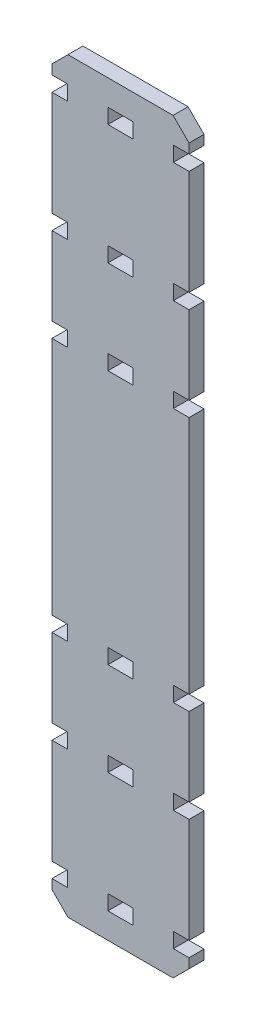
SolidWorks part; units mm, degrees
ref_plane "Front" through (0, 0, 0) normal (0, 0, 1) x (1, 0, 0)
ref_plane "Top" through (0, 0, 0) normal (0, 1, 0) x (1, 0, 0)
ref_plane "Right" through (0, 0, 0) normal (1, 0, 0) x (0, 0, -1)
ref_axis "side-side" through (80.9, 0, 0) along (-1, 0, 0)
ref_axis "up-down" through (0, 50, 0) along (0, -1, 0)
ref_axis "front-back" through (0, 0, -80.9) along (0, 0, 1)
sketch "Sketch1" plane through (0, 0, 0) normal (0, 0, 1) x (1, 0, 0)
  line L0 (21.7993, 110.6625) -> (21.7993, 118.7905) construction
  line L1 (43.5986, 118.7905) -> (0, 118.7905)
  line L2 (43.5986, 118.7905) -> (43.5986, 110.6625)
  line L3 (43.5986, -118.7905) -> (0, -118.7905)
  line L4 (0, 118.7905) -> (0, 110.6625)
  line L5 (25.7993, 110.6625) -> (17.7993, 110.6625)
  line L6 (5, 110.6625) -> (-15, 110.6625) construction
  line L7 (0, -110.6625) -> (5, -110.6625) construction
  line L8 (43.5986, 105.9) -> (38.5986, 105.9) construction
  line L9 (0, 110.6625) -> (5, 110.6625)
  line L10 (25.7993, 110.6625) -> (25.7993, 105.9)
  line L11 (0, 105.9) -> (5, 105.9)
  line L12 (5, 110.6625) -> (5, 105.9)
  line L13 (43.5986, 110.6625) -> (38.5986, 110.6625) construction
  line L14 (38.5986, 110.6625) -> (43.5986, 110.6625)
  line L15 (38.5986, 110.6625) -> (38.5986, 105.9)
  line L16 (38.5986, 105.9) -> (43.5986, 105.9)
  line L17 (43.5986, 105.9) -> (43.5986, 72.5625)
  line L18 (0, 105.9) -> (0, 72.5625)
  line L19 (25.7993, 105.9) -> (17.7993, 105.9)
  line L20 (17.7993, 110.6625) -> (17.7993, 105.9)
  line L21 (43.5986, 72.5625) -> (38.5986, 72.5625) construction
  line L22 (38.5986, 72.5625) -> (43.5986, 72.5625)
  line L23 (38.5986, 72.5625) -> (38.5986, 67.8)
  line L24 (38.5986, 67.8) -> (43.5986, 67.8)
  line L25 (43.5986, 38.1) -> (43.5986, -38.1)
  line L26 (43.5986, 67.8) -> (38.5986, 67.8) construction
  line L27 (5, 72.5625) -> (0, 72.5625)
  line L28 (5, 72.5625) -> (5, 67.8)
  line L29 (5, 67.8) -> (0, 67.8)
  line L31 (43.5986, 42.8625) -> (38.5986, 42.8625) construction
  line L32 (38.5986, 42.8625) -> (43.5986, 42.8625)
  line L33 (38.5986, 42.8625) -> (38.5986, 38.1)
  line L34 (38.5986, 38.1) -> (43.5986, 38.1)
  line L35 (0, 67.8) -> (0, 42.8625)
  line L36 (43.5986, 38.1) -> (38.5986, 38.1) construction
  line L37 (0, 42.8625) -> (5, 42.8625)
  line L39 (0, 38.1) -> (5, 38.1)
  line L40 (5, 42.8625) -> (5, 38.1)
  line L41 (25.7993, 72.5625) -> (17.7993, 72.5625)
  line L42 (25.7993, 72.5625) -> (25.7993, 67.8)
  line L43 (25.7993, 67.8) -> (17.7993, 67.8)
  line L44 (17.7993, 72.5625) -> (17.7993, 67.8)
  line L45 (25.7993, 42.8625) -> (17.7993, 42.8625)
  line L46 (25.7993, 42.8625) -> (25.7993, 38.1)
  line L47 (25.7993, 38.1) -> (17.7993, 38.1)
  line L48 (17.7993, 42.8625) -> (17.7993, 38.1)
  line L49 (-15, -38.1) -> (5, -38.1) construction
  line L50 (38.5986, -38.1) -> (43.5986, -38.1)
  line L51 (38.5986, -38.1) -> (38.5986, -42.8625)
  line L52 (38.5986, -42.8625) -> (43.5986, -42.8625)
  line L53 (0, -42.8625) -> (0, -67.8)
  line L54 (-15, -67.8) -> (5, -67.8) construction
  line L55 (38.5986, -67.8) -> (43.5986, -67.8)
  line L56 (38.5986, -67.8) -> (38.5986, -72.5625)
  line L57 (38.5986, -72.5625) -> (43.5986, -72.5625)
  line L58 (43.5986, -42.8625) -> (43.5986, -67.8)
  line L59 (0, -105.9) -> (5, -105.9) construction
  line L60 (38.5986, -105.9) -> (43.5986, -105.9)
  line L61 (38.5986, -105.9) -> (38.5986, -110.6625)
  line L62 (38.5986, -110.6625) -> (43.5986, -110.6625)
  line L63 (43.5986, -72.5625) -> (43.5986, -105.9)
  line L64 (-15, -42.8625) -> (5, -42.8625) construction
  line L65 (5, -105.9) -> (0, -105.9)
  line L66 (5, -105.9) -> (5, -110.6625)
  line L67 (5, -110.6625) -> (0, -110.6625)
  line L68 (0, -72.5625) -> (0, -105.9)
  line L69 (5, -67.8) -> (0, -67.8)
  line L70 (5, -67.8) -> (5, -72.5625)
  line L71 (5, -72.5625) -> (0, -72.5625)
  line L72 (43.5986, -110.6625) -> (43.5986, -118.7905)
  line L73 (5, -38.1) -> (0, -38.1)
  line L74 (5, -38.1) -> (5, -42.8625)
  line L75 (5, -42.8625) -> (0, -42.8625)
  line L76 (43.5986, 67.8) -> (43.5986, 42.8625)
  line L77 (25.7993, -38.1) -> (17.7993, -38.1)
  line L78 (25.7993, -38.1) -> (25.7993, -42.8625)
  line L79 (25.7993, -42.8625) -> (17.7993, -42.8625)
  line L80 (17.7993, -38.1) -> (17.7993, -42.8625)
  line L81 (-15, -72.5625) -> (5, -72.5625) construction
  line L82 (17.7993, -67.8) -> (25.7993, -67.8)
  line L83 (17.7993, -67.8) -> (17.7993, -72.5625)
  line L84 (17.7993, -72.5625) -> (25.7993, -72.5625)
  line L85 (25.7993, -67.8) -> (25.7993, -72.5625)
  line L86 (0, -110.6625) -> (5, -110.6625) construction
  line L87 (17.7993, -105.9) -> (25.7993, -105.9)
  line L88 (17.7993, -105.9) -> (17.7993, -110.6625)
  line L89 (17.7993, -110.6625) -> (25.7993, -110.6625)
  line L90 (25.7993, -105.9) -> (25.7993, -110.6625)
  line L91 (0, -110.6625) -> (0, -118.7905)
  line L92 (0, 38.1) -> (0, -38.1)
  point P17 (2.5, -110.6625)
  point P44 (0, 0)
  dimension "D1" = 8.128
  dimension "D2" = 43.5986
  dimension "D3" = 8.128
  dimension "D4" = 5
  dimension "D5" = 8
extrude "Boss-Extrude1" add sketch "Sketch1" along normal blind 4.7625
chamfer "Chamfer1" distance 5.08 angle 45 4 edges at (43.5986, 118.7905, 2.3813) (0, 118.7905, 2.3813) (43.5986, -118.7905, 2.3813) (0, -118.7905, 2.3813)
